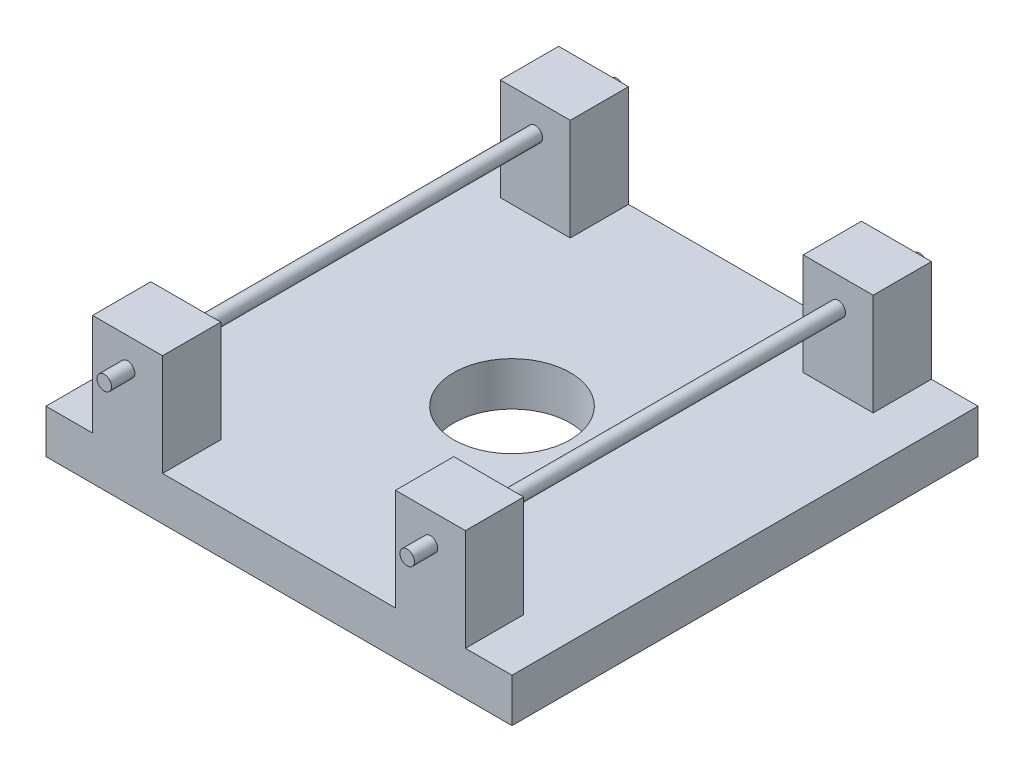
SolidWorks part; units mm, degrees
ref_plane "Front Plane" through (0, 0, 0) normal (0, 0, 1) x (1, 0, 0)
ref_plane "Top Plane" through (0, 0, 0) normal (0, 1, 0) x (1, 0, 0)
ref_plane "Right Plane" through (0, 0, 0) normal (1, 0, 0) x (0, 0, -1)
sketch "Sketch3" plane through (0, 0, 0) normal (0, 1, 0) x (1, 0, 0)
  line L1 (-25.4, 25.4) -> (25.4, 25.4)
  line L2 (-25.4, 25.4) -> (-25.4, -25.4)
  line L3 (-25.4, -25.4) -> (25.4, -25.4)
  line L4 (25.4, 25.4) -> (25.4, -25.4)
  line L5 (-25.4, 25.4) -> (25.4, -25.4) construction
  line L6 (-25.4, -25.4) -> (25.4, 25.4) construction
  point P0 (0, 0)
  dimension "D1" = 50.8
  dimension "D2" = 50.8
extrude "Boss-Extrude2" add sketch "Sketch3" along normal blind 4.7625
sketch "Sketch4" plane through (0, 4.7625, 0) normal (0, 1, 0) x (1, 0, 0)
  circle A0 centre (0, 0) radius 6.35
extrude "Cut-Extrude2" cut sketch "Sketch4" against normal through all
sketch "Sketch5" plane through (0, 4.7625, 0) normal (0, 1, 0) x (1, 0, 0)
  line L0 (25.4, 25.4) -> (-25.4, 25.4) construction
  line L1 (-20.32, 25.4) -> (-12.7, 25.4)
  line L2 (-20.32, 25.4) -> (-20.32, -25.4)
  line L3 (-20.32, -25.4) -> (-12.7, -25.4)
  line L4 (-12.7, 25.4) -> (-12.7, -25.4)
  line L9 (0, 0) -> (0, 19.1256) construction
  line L10 (20.32, -25.4) -> (12.7, -25.4)
  line L11 (20.32, 25.4) -> (12.7, 25.4)
  line L12 (20.32, 25.4) -> (20.32, -25.4)
  line L13 (12.7, 25.4) -> (12.7, -25.4)
  dimension "D1" = 50.8
  dimension "D2" = 7.62
  dimension "D3" = 12.7
extrude "Boss-Extrude3" add sketch "Sketch5" along normal blind 11.1125
sketch "Sketch6" plane through (0, 15.875, 0) normal (0, 1, 0) x (1, 0, 0)
  line L0 (0, 0) -> (0, 12.0892) construction
  line L1 (-20.32, 25.4) -> (-20.32, -25.4) construction
  line L2 (-20.32, 19.05) -> (-12.7, 19.05)
  line L3 (-20.32, 19.05) -> (-20.32, -19.05)
  line L4 (-20.32, -19.05) -> (-12.7, -19.05)
  line L5 (-12.7, 19.05) -> (-12.7, -19.05)
  line L6 (-12.7, -25.4) -> (-12.7, 25.4) construction
  line L7 (-12.7, 25.4) -> (-20.32, 25.4) construction
  line L8 (-20.32, -25.4) -> (-12.7, -25.4) construction
  line L9 (20.32, -19.05) -> (12.7, -19.05)
  line L10 (12.7, 19.05) -> (12.7, -19.05)
  line L11 (20.32, 19.05) -> (20.32, -19.05)
  line L12 (20.32, 19.05) -> (12.7, 19.05)
  dimension "D1" = 6.35
  dimension "D2" = 6.35
extrude "Cut-Extrude3" cut sketch "Sketch6" against normal up to surface (11.1125 mm away) contours L11 L12 L10 L9 | L3 L2 L5 L4 region at (16.51, 15.875, 0) up to face at (0, 4.7625, 6.35)
sketch "Sketch7" plane through (0, 0, 25.4) normal (0, 0, 1) x (1, 0, 0)
  line L0 (-20.32, 15.875) -> (-12.7, 15.875) construction
  line L1 (-20.32, 15.875) -> (-20.32, 4.7625) construction
  line L2 (12.7, 15.875) -> (20.32, 15.875) construction
  line L3 (12.7, 15.875) -> (12.7, 4.7625) construction
  circle A0 centre (-16.51, 12.7) radius 0.7937
  circle A1 centre (16.51, 12.7) radius 0.7937
  dimension "D1" = 1.5875
  dimension "D2" = 3.175
  dimension "D3" = 3.81
  dimension "D4" = 3.175
  dimension "D5" = 3.81
extrude "Boss-Extrude4" add sketch "Sketch7" along normal blind 2.54 and the other way blind 53.34
